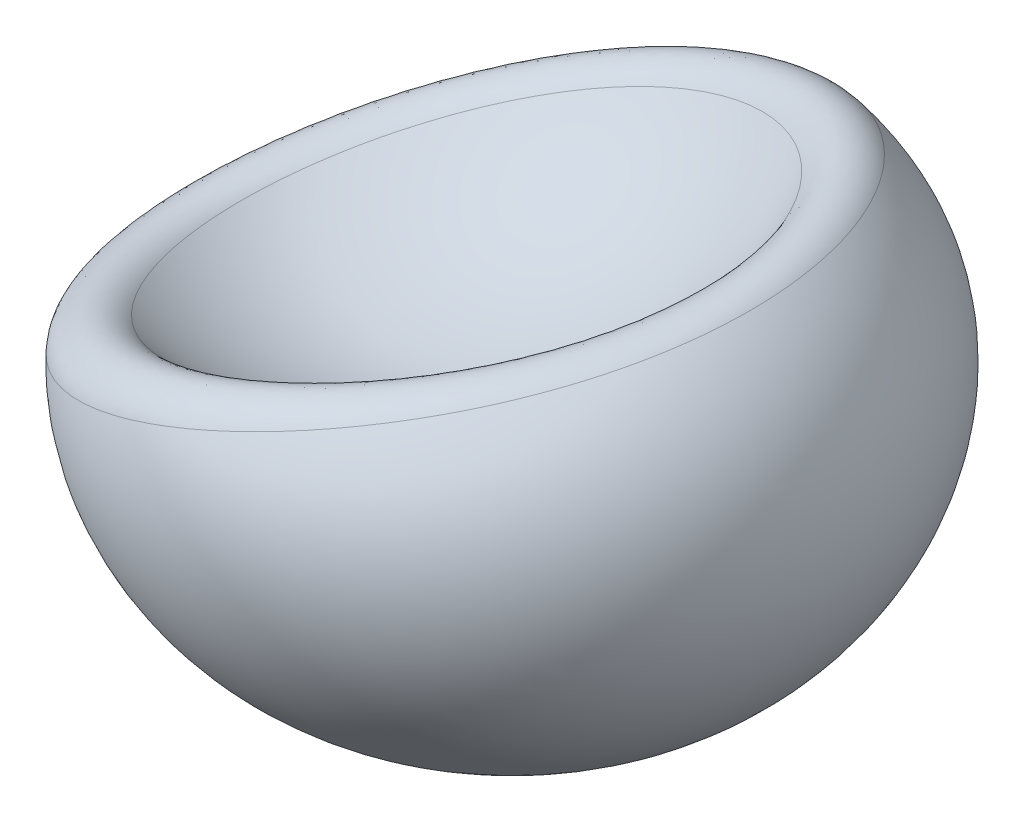
SolidWorks part; units mm, degrees
ref_plane "Front Plane" through (0, 0, 0) normal (0, 0, 1) x (1, 0, 0)
ref_plane "Top Plane" through (0, 0, 0) normal (0, 1, 0) x (1, 0, 0)
ref_plane "Right Plane" through (0, 0, 0) normal (1, 0, 0) x (0, 0, -1)
sketch "Sketch1" plane through (0, 0, 0) normal (0, 0, 1) x (1, 0, 0)
  line L0 (0, 0) -> (0, 60) construction
  line L1 (0, 0) -> (20, 0)
  line L2 (0, 0) -> (0, 60)
  spline S0 degree 3 poles (20, 0) (51.9999, 12.3997) (56.6302, 61.8779) (0, 60) knots 0 0 0 0 1 1 1 1
  dimension "D1" = 60
  dimension "D2" = 20
revolve "Revolve1" add sketch "Sketch1" angle 360 about L0
sketch "Sketch2" plane through (0, 0, 0) normal (0, 0, 1) x (1, 0, 0)
  line L0 (12.3353, 102.1446) -> (-41.1031, 36.0436) construction
  line L1 (12.3353, 102.1446) -> (-41.1031, 36.0436)
  arc A0 (12.3353, 102.1446) -> (-41.1031, 36.0436) centre (-14.3839, 69.0941) cw
  dimension "D1" = 85
revolve "Cut-Revolve1" cut sketch "Sketch2" angle 360 about L0
sketch "Sketch3" plane through (0, 0, 0) normal (0, 0, 1) x (1, 0, 0)
  line L0 (-43.8701, 38.5841) -> (25.6676, 55.5595) construction
  line L1 (-9.1012, 47.0718) -> (-3.8248, 25.4573) construction
  line L2 (-3.8248, 25.4573) -> (-3.8248, 70.27) construction
ref_plane "Plane1" through (0, 50, 0) normal (0, 1, 0) x (1, 0, 0)
sketch "Sketch5" plane through (0, 50, 0) normal (0, 1, 0) x (1, 0, 0)
  line L0 (-43.8701, 0) -> (25.6676, 0) construction
  line L1 (-9.1012, 0) -> (-3.8248, 0) construction
  circle A0 centre (-3.8248, 0) radius 1.5
  dimension "D1" = 3
extrude "Cut-Extrude1" cut sketch "Sketch5" against normal blind 35
fillet "Fillet1" radius 5 1 edges at (-42.6451, 37.5878, -3.8612)
